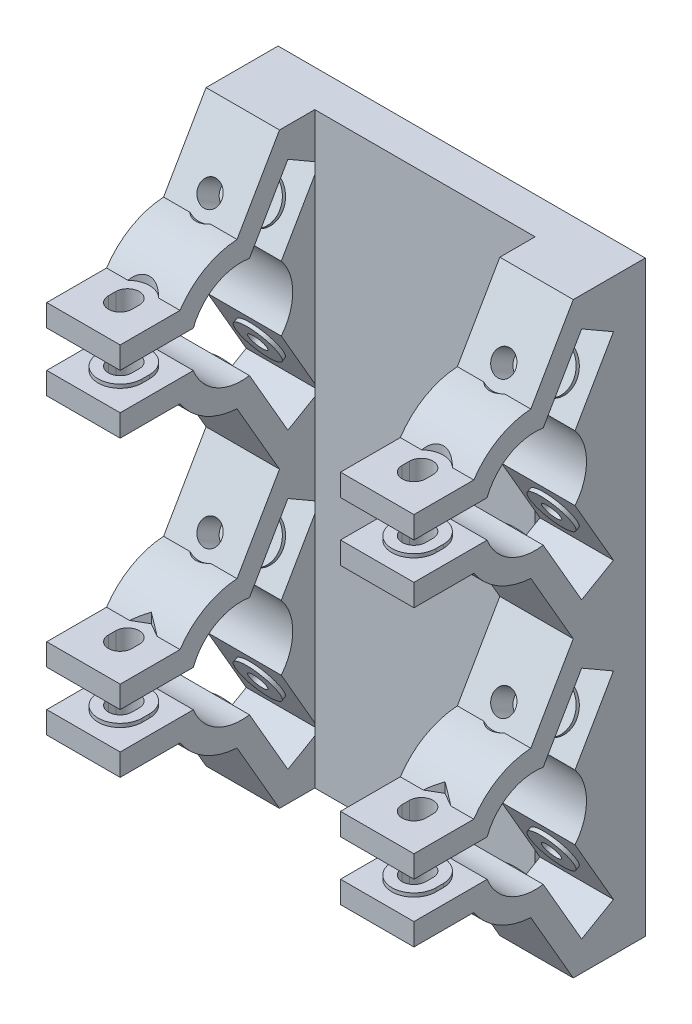
SolidWorks part; units mm, degrees
ref_plane "Спереди" through (0, 0, 0) normal (0, 0, 1) x (1, 0, 0)
ref_plane "Сверху" through (0, 0, 0) normal (0, 1, 0) x (1, 0, 0)
ref_plane "Справа" through (0, 0, 0) normal (1, 0, 0) x (0, 0, -1)
sketch "Эскиз1" plane through (0, 0, 0) normal (1, 0, 0) x (0, 0, -1)
  line L0 (0, 40) -> (0, -40)
  line L1 (0, -40) -> (5, -40)
  line L2 (5, -40) -> (5, 40)
  line L3 (5, 40) -> (0, 40)
  line L4 (-54.4681, 0) -> (-52.8723, 0) construction
  line L5 (-53.8298, 20) -> (-1.5957, 20) construction
  line L6 (-10, 20) -> (-4.0021, 30.3886) construction
  line L7 (-10, 20) -> (-4.0021, 9.6114) construction
  line L8 (-8.8959, 26.9124) -> (-3.6651, 35.9724)
  line L9 (-3.6651, 35.9724) -> (0.6651, 33.4724)
  line L10 (0.6651, 33.4724) -> (-4.5658, 24.4124)
  line L11 (-4.5658, 15.5876) -> (0.6651, 6.5276)
  line L12 (0.6651, 6.5276) -> (-3.6651, 4.0276)
  line L13 (-3.6651, 4.0276) -> (-8.8959, 13.0876)
  line L14 (-7.5263, 14.5) -> (-6.4737, 15.1077) construction
  line L15 (-7.5263, 25.5) -> (-6.4737, 24.8923) construction
  line L16 (-16.5383, 17.5) -> (-26.5, 17.5)
  line L17 (-26.5, 17.5) -> (-26.5, 14.5)
  line L18 (-26.5, 14.5) -> (-18.3516, 14.5)
  line L19 (-10.5873, 10.0173) -> (-4.8038, 0)
  line L20 (-4.8038, 0) -> (0, 0)
  line L21 (-16.5383, 22.5) -> (-26.5, 22.5)
  line L22 (-26.5, 22.5) -> (-26.5, 25.5)
  line L23 (-26.5, 25.5) -> (-18.3516, 25.5)
  line L24 (-10.5873, 29.9827) -> (-4.8038, 40)
  line L25 (-16, 18.4961) -> (-16, 21.5039) construction
  line L26 (-4.8038, 40) -> (0, 40)
  arc A0 (-4.5658, 15.5876) -> (-4.5658, 24.4124) centre (-10, 20) ccw
  arc A1 (-8.8959, 26.9124) -> (-16.5383, 22.5) centre (-10, 20) ccw
  arc A2 (-8.8959, 13.0876) -> (-16.5383, 17.5) centre (-10, 20) cw
  circle A3 centre (-10, 20) radius 6 construction
  arc A4 (-18.3516, 14.5) -> (-10.5873, 10.0173) centre (-10, 20) ccw
  arc A5 (-18.3516, 25.5) -> (-10.5873, 29.9827) centre (-10, 20) cw
  point P4 (0, 0)
  point P28 (-1.5, 34.7224)
  point P29 (-7, 25.1962)
  point P30 (-1.5, 5.2776)
  point P31 (-1.5, 5.2776)
  point P32 (-7, 14.8038)
  point P47 (-16, 20)
  dimension "D4" = 7
  dimension "D6" = 12
  dimension "D16" = 3
  dimension "D1" = 5
  dimension "D2" = 80
  dimension "D3" = 20
  dimension "D5" = 10
  dimension "D7" = 120
  dimension "D8" = 60
  dimension "D9" = 5
  dimension "D10" = 5
  dimension "D11" = 11
  dimension "D12" = 11
  dimension "D13" = 10.5
  dimension "D14" = 5
  dimension "D15" = 3
  dimension "D17" = 3
  dimension "D18" = 3
extrude "Бобышка-Вытянуть1" add sketch "Эскиз1" along normal blind 50 contours L0 L1 L2 L3
extrude "Бобышка-Вытянуть2" add sketch "Эскиз1<3>" along normal blind 10 contours L18 A4 L19 L20 L0 L12 L13 A2 L16 L17 | A0 L11 L0 L10 | A5 L23 L22 L21 A1 L8 L9 L0 L26 L24 region at (0, 0.3176, 2.4019) region at (0, 20, 1.6399) region at (0, 36.9282, 0.3176)
sketch "Эскиз1<3>" plane through (0, 0, 0) normal (1, 0, 0) x (0, 0, -1) same geometry as "Эскиз1"
ref_axis "Ось1" through (10, 20, 10) along (-1, 0, 0)
sketch "Эскиз6" plane through (0, 8.0801, 13.9952) normal (0, 0.5, 0.866) x (1, 0, 0)
  line L0 (0, 25.5074) -> (10, 25.5074)
  line L1 (0, 27.9904) -> (0, 18.8589) construction
  line L2 (10, 27.9904) -> (10, 18.8589) construction
  line L3 (10, 25.5074) -> (10, 29.3205)
  line L4 (10, 29.3205) -> (0, 29.3205)
  line L5 (0, 29.3205) -> (0, 25.5074)
  line L6 (10, 12.3205) -> (0, 12.3205) construction
  dimension "D1" = 17
extrude "Вырез-Вытянуть10" cut sketch "Эскиз6" along normal blind 1
sketch "Эскиз2" plane through (0, 8.0801, 13.9952) normal (0, 0.5, 0.866) x (1, 0, 0)
  line L0 (10, 12.3205) -> (0, 12.3205) construction
  line L1 (5, -6.6465) -> (5, 40.453) construction
  line L2 (10, -2.4019) -> (0, -2.4019) construction
  circle A0 centre (5, 23.3205) radius 1.25
  circle A1 centre (5, 23.3205) radius 1.6
  circle A2 centre (5, 23.3205) radius 3
  point P6 (5, -2.4019)
  dimension "D2" = 2.5
  dimension "D3" = 3.2
  dimension "D4" = 6
  dimension "D1" = 11
extrude "Бобышка-Вытянуть3" add sketch "Эскиз2" along normal blind 0.5 contours A2
extrude "Бобышка-Вытянуть4" add sketch "Эскиз2<3>" against normal blind 0.5 from offset 5 contours A2
sketch "Эскиз2<3>" plane through (0, 8.0801, 13.9952) normal (0, 0.5, 0.866) x (1, 0, 0) same geometry as "Эскиз2"
extrude "Вырез-Вытянуть1" cut sketch "Эскиз2<4>" against normal blind 10 from offset 0.5 contours A0
sketch "Эскиз2<4>" plane through (0, 8.0801, 13.9952) normal (0, 0.5, 0.866) x (1, 0, 0) same geometry as "Эскиз2"
extrude "Вырез-Вытянуть4" cut sketch "Эскиз2<5>" along normal blind 1 from offset 8 contours A2
sketch "Эскиз2<5>" plane through (0, 8.0801, 13.9952) normal (0, 0.5, 0.866) x (1, 0, 0) same geometry as "Эскиз2"
extrude "Вырез-Вытянуть5" cut sketch "Эскиз2<6>" along normal blind 3.5 from offset 4.5 contours A1
sketch "Эскиз2<6>" plane through (0, 8.0801, 13.9952) normal (0, 0.5, 0.866) x (1, 0, 0) same geometry as "Эскиз2"
ref_plane "Плоскость2" through (0, 20, 0) normal (0, -1, 0) x (-1, 0, 0)
mirror "Зеркальное отражение3" about plane through (0, 20, 0) normal (0, -1, 0) of "Вырез-Вытянуть10", "Бобышка-Вытянуть3", "Бобышка-Вытянуть4", "Вырез-Вытянуть1", "Вырез-Вытянуть4", "Вырез-Вытянуть5"
sketch "Эскиз3" plane through (0, 25.5, 0) normal (0, 1, 0) x (1, 0, 0)
  line L0 (10, -26.5) -> (0, -26.5) construction
  line L1 (5, -30.7803) -> (5, -14.9973) construction
  line L2 (5, -20.5) -> (5, -21.5) construction
  line L3 (6.6, -20.5) -> (6.6, -21.5)
  line L4 (3.4, -20.5) -> (3.4, -21.5)
  line L5 (5, -20.5) -> (5, -21.5) construction
  line L6 (8, -20.5) -> (8, -21.5)
  line L7 (2, -20.5) -> (2, -21.5)
  line L8 (10, -10) -> (0, -10) construction
  arc A0 (6.6, -20.5) -> (3.4, -20.5) centre (5, -20.5) ccw
  arc A1 (3.4, -21.5) -> (6.6, -21.5) centre (5, -21.5) ccw
  arc A2 (8, -20.5) -> (2, -20.5) centre (5, -20.5) ccw
  arc A3 (2, -21.5) -> (8, -21.5) centre (5, -21.5) ccw
  point P0 (5, -26.5)
  point P7 (5, -21)
  point P12 (5, -21)
  dimension "D2" = 1.6
  dimension "D3" = 3
  dimension "D1" = 1
  dimension "D4" = 10.5
extrude "Бобышка-Вытянуть5" add sketch "Эскиз3" against normal blind 0.5 from offset 3 contours A3 L6 A2 L7 offset against normal yes
extrude "Бобышка-Вытянуть6" add sketch "Эскиз3<3>" along normal blind 0.5 from offset 8 contours A3 L6 A2 L7 offset against normal yes
sketch "Эскиз3<3>" plane through (0, 25.5, 0) normal (0, 1, 0) x (1, 0, 0) same geometry as "Эскиз3"
extrude "Вырез-Вытянуть6" cut sketch "Эскиз3<4>" along normal blind 2
sketch "Эскиз3<4>" plane through (0, 25.5, 0) normal (0, 1, 0) x (1, 0, 0) same geometry as "Эскиз3"
extrude "Вырез-Вытянуть7" cut sketch "Эскиз3<6>" against normal blind 11 contours A1 L3 A0 L4
sketch "Эскиз3<6>" plane through (0, 25.5, 0) normal (0, 1, 0) x (1, 0, 0) same geometry as "Эскиз3"
sketch "Эскиз4" plane through (0, 14.5, 0) normal (0, -1, 0) x (1, 0, 0)
  line L1 (5, 17.2668) -> (7.8, 18.8834)
  line L2 (7.8, 18.8834) -> (7.8, 22.1166)
  line L3 (7.8, 22.1166) -> (5, 23.7332)
  line L4 (5, 23.7332) -> (2.2, 22.1166)
  line L5 (2.2, 22.1166) -> (2.2, 18.8834)
  line L6 (2.2, 18.8834) -> (5, 17.2668)
  circle A0 centre (5, 20.5) radius 2.8 construction
  dimension "D1" = 5.6
extrude "Вырез-Вытянуть8" cut sketch "Эскиз4" along normal blind 2
ref_plane "Плоскость1" through (25, 0, 0) normal (1, 0, 0) x (0, 0, -1)
mirror "Зеркальное отражение6" about plane through (25, 0, 0) normal (1, 0, 0) of "Вырез-Вытянуть8", "Вырез-Вытянуть7", "Вырез-Вытянуть6", "Бобышка-Вытянуть6", "Бобышка-Вытянуть5", "Зеркальное отражение3", "Вырез-Вытянуть5", "Вырез-Вытянуть4", "Вырез-Вытянуть1", "Бобышка-Вытянуть4", "Бобышка-Вытянуть3", "Вырез-Вытянуть10", "Бобышка-Вытянуть2"
mirror "Зеркальное отражение7" about plane through (10, 0, 0) normal (0, 1, 0) of "Зеркальное отражение6", "Вырез-Вытянуть8", "Вырез-Вытянуть7", "Вырез-Вытянуть6", "Бобышка-Вытянуть6", "Бобышка-Вытянуть5", "Зеркальное отражение3", "Вырез-Вытянуть5", "Вырез-Вытянуть4", "Вырез-Вытянуть1", "Бобышка-Вытянуть4", "Бобышка-Вытянуть3", "Вырез-Вытянуть10", "Бобышка-Вытянуть2"
